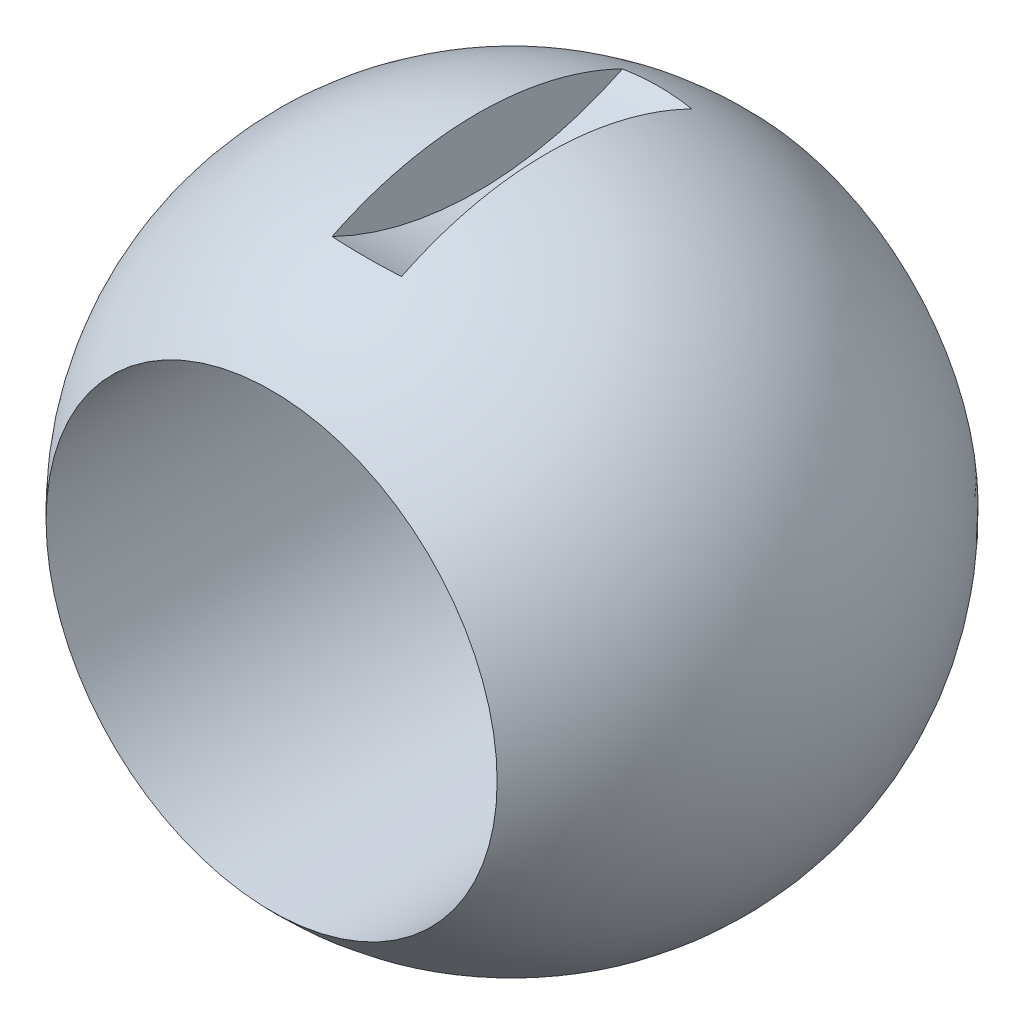
SolidWorks part; units mm, degrees
material "AISI Typ 316L stal nierdzewna"
ref_plane "Przednia" through (0, 0, 0) normal (0, 0, 1) x (1, 0, 0)
ref_plane "Górna" through (0, 0, 0) normal (0, 1, 0) x (1, 0, 0)
ref_plane "Prawa" through (0, 0, 0) normal (1, 0, 0) x (0, 0, -1)
sketch "Szkic1" plane through (0, 0, 0) normal (0, 0, 1) x (1, 0, 0)
  line L0 (0, -27.5475) -> (0, 33.9654) construction
  arc A0 (0, -19) -> (0, 19) centre (0, 0) ccw
  circle A1 centre (0, 0) radius 13
  dimension "D1" = 38
  dimension "D2" = 26
revolve "Obrót1" add sketch "Szkic1" angle 360 about L0 region at (0.4249, -16, 0) region at (5.5174, 0, 0)
sketch "Szkic2" plane through (0, 0, 0) normal (0, 0, 1) x (1, 0, 0)
  circle A0 centre (0, 0) radius 13
  dimension "D1" = 26
extrude "Wytnij-wyciągnięcie1" cut sketch "Szkic2" against normal through all both and the other way through all
sketch "Szkic3" plane through (0, 0, 0) normal (0, 1, 0) x (1, 0, 0)
  line L0 (0, 16.9544) -> (0, -19.2217) construction
  line L2 (-2, -8) -> (2, -8)
  line L3 (-2, -8) -> (-2, 8)
  line L4 (-2, 8) -> (2, 8)
  line L5 (2, -8) -> (2, 8)
  line L6 (-2, -8) -> (2, 8) construction
  line L7 (-2, 8) -> (2, -8) construction
  point P2 (0, 0)
  dimension "D1" = 4
  dimension "D2" = 16
sketch "Szkic5" plane through (0, 0, 0) normal (1, 0, 0) x (0, 0, -1)
  line L0 (0, 0) -> (0, 34) construction
  line L1 (-8, 0) -> (8, 0) construction
  circle A0 centre (0, 34) radius 19
  dimension "D2" = 38
  dimension "D1" = 34
extrude "Wytnij-wyciągnięcie4" cut sketch "Szkic5" against normal blind 2 and the other way blind 2
